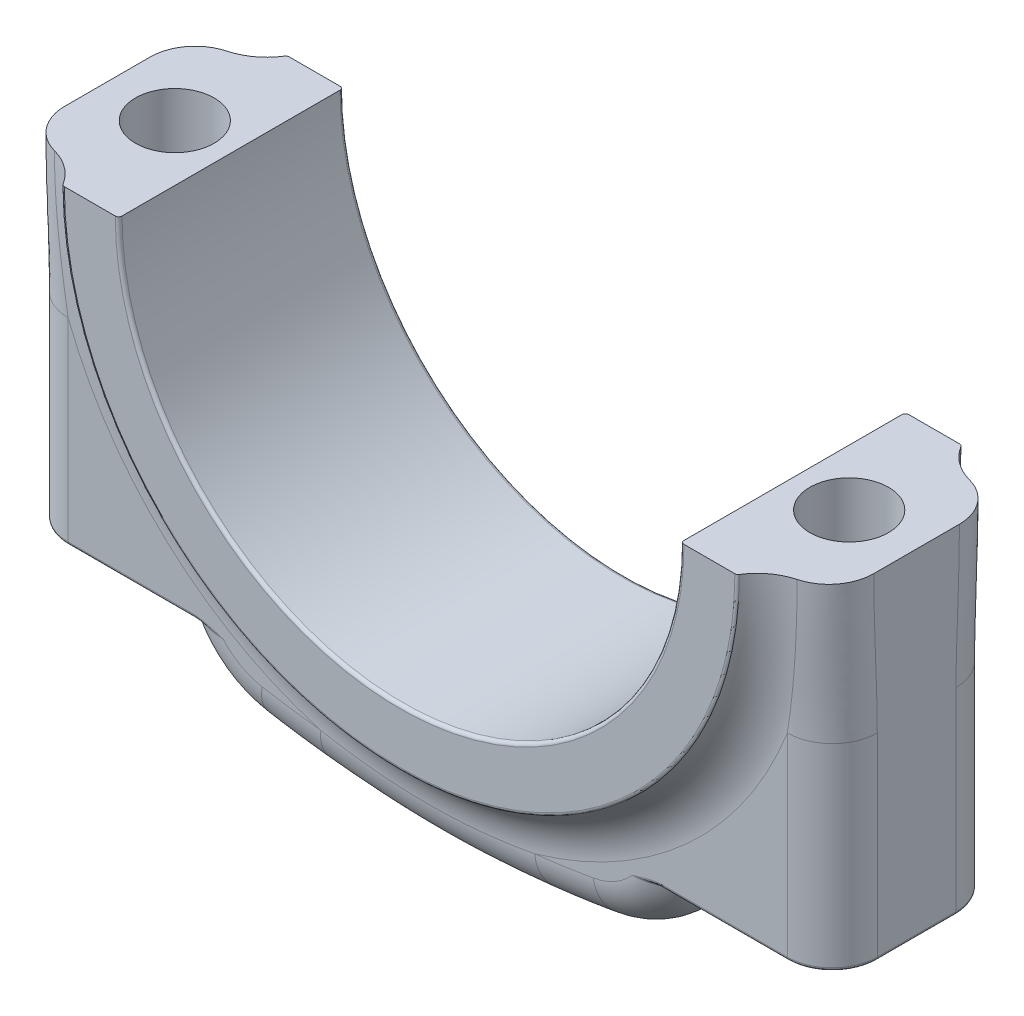
SolidWorks part; units mm, degrees
material "1060 Alloy"
ref_plane "Front Plane" through (0, 0, 0) normal (0, 0, 1) x (1, 0, 0)
ref_plane "Top Plane" through (0, 0, 0) normal (0, 1, 0) x (1, 0, 0)
ref_plane "Right Plane" through (0, 0, 0) normal (1, 0, 0) x (0, 0, -1)
sketch "Sketch1" plane through (0, 0, 0) normal (0, 0, 1) x (1, 0, 0)
  line L0 (0, -25) -> (0, -37.5136)
  line L1 (25, 0) -> (36, 0)
  line L2 (36, 0) -> (36, -30)
  line L3 (0, -37.5136) -> (59.726, -37.5136) construction
  arc A0 (0, -25) -> (25, 0) centre (0, 0) ccw
  arc A1 (0, -37.5136) -> (36, -30) centre (0, 52.4864) ccw
  dimension "D1" = 25
  dimension "D2" = 90
  dimension "D3" = 36
  dimension "D4" = 30
extrude "Boss-Extrude1" add sketch "Sketch1" along normal blind 7.5
sketch "Sketch2" plane through (0, 0, 7.5) normal (0, 0, 1) x (1, 0, 0)
  line L1 (36, 0) -> (25, 0) construction
  line L2 (25, 0) -> (30, 0)
  line L3 (0, -25) -> (0, -30)
  line L4 (0, -25) -> (0, -37.5136) construction
  arc A0 (0, -25) -> (25, 0) centre (0, 0) ccw construction
  arc A1 (0, -25) -> (25, 0) centre (0, 0) ccw
  arc A2 (0, -30) -> (30, 0) centre (0, 0) ccw
  dimension "D1" = 30
extrude "Boss-Extrude2" add sketch "Sketch2" along normal blind 2.5
fillet "Fillet1" radius 5 1 edges at (21.2132, -21.2132, 7.5)
hole_wizard "Ø7.0 (7) Diameter Hole1" positions "Sketch3" profile "Sketch5" hole size "Ø7.0" standard "DIN" end condition through all
sketch "Sketch3" plane through (0, 0, 0) normal (0, 1, 0) x (1, 0, 0)
  line L0 (36, 0) -> (25, 0) construction
  point P0 (30, 0)
  dimension "D1" = 30
sketch "Sketch5" plane through (30, 0, 0) normal (1, 0, 0) x (0, 0, 1)
  line L0 (0, 0) -> (0, 37.5136)
  line L1 (0, 37.5136) -> (3.5, 37.5136)
  line L2 (3.5, 37.5136) -> (3.5, 0)
  line L5 (3.5, 0) -> (0, 0)
  line L11 (0, -6.35) -> (0, 107.95) construction
  dimension "Thru Hole Dia." = 7
  dimension "Thru Hole Depth" = 37.5136
ref_plane "Plane1" through (0, -30, 0) normal (0, 1, 0) x (1, 0, 0)
sketch "Sketch6" plane through (0, -30, 0) normal (0, 1, 0) x (1, 0, 0)
  line L0 (0, -10) -> (25, -10) construction
  line L1 (23, -10) -> (36, -10)
  line L2 (23, -10) -> (23, 0)
  line L3 (23, 0) -> (36, 0)
  line L4 (36, -10) -> (36, 0)
  line L5 (23, -10) -> (36, 0) construction
  line L6 (23, 0) -> (36, -10) construction
  line L7 (25, 0) -> (0, 0) construction
  point P0 (29.5, -5)
  dimension "D1" = 23
extrude "Cut-Extrude1" cut sketch "Sketch6" against normal through all
fillet "Fillet2" radius 10 1 edges at (23, -34.5251, 3.75)
fillet "Fillet3" radius 4 3 edges at (20.0132, -34.085, 7.5) (7.7331, -37.1808, 7.5) (36, -15, 7.5)
fillet "Fillet4" radius 0.3 7 edges at (23, -30, 1.75) (36, -30, 1.75) (34.8284, -30, 6.3284) (21.5426, -30, 6.4868) (25.2227, -30, 7.5) (21.2132, -21.2132, 10) (17.6777, -17.6777, 10)
mirror "Mirror1" about plane through (0, 0, 0) normal (1, 0, 0) of bodies 106 101
mirror "Mirror2" about plane through (0, 0, 0) normal (0, 0, 1) of bodies 102 103
